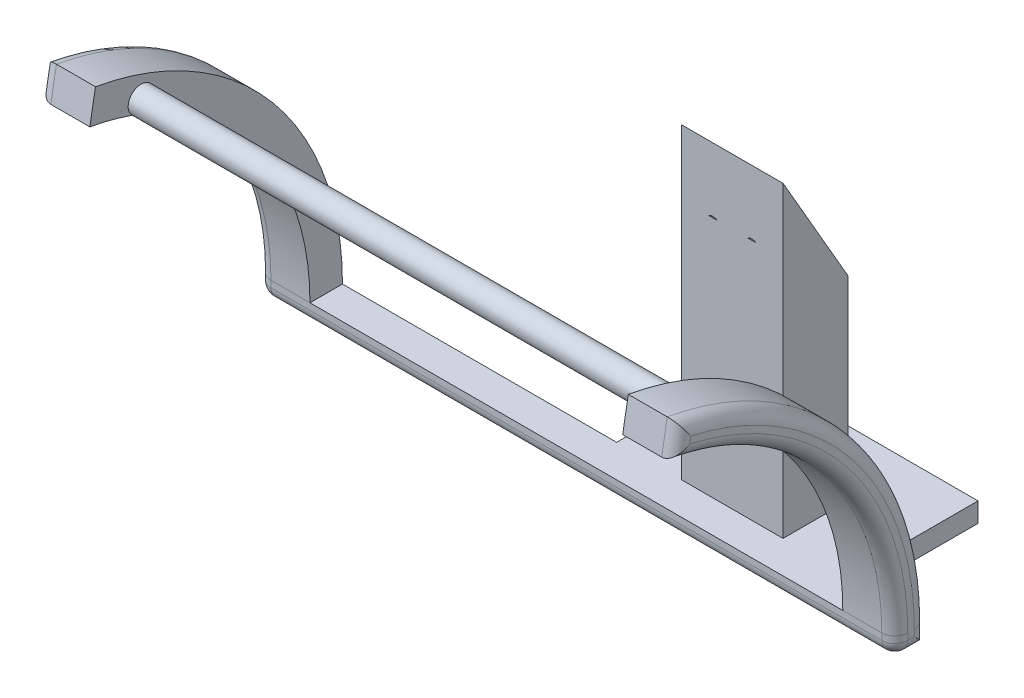
SolidWorks part; units mm, degrees
ref_plane "Front Plane" through (0, 0, 0) normal (0, 0, 1) x (1, 0, 0)
ref_plane "Top Plane" through (0, 0, 0) normal (0, 1, 0) x (1, 0, 0)
ref_plane "Right Plane" through (0, 0, 0) normal (1, 0, 0) x (0, 0, -1)
sketch "Sketch1" plane through (0, 0, 0) normal (0, 1, 0) x (1, 0, 0)
  line L0 (-8.4368, 20.25) -> (-8.4368, 0.25) construction
  line L1 (-26.2418, 20.25) -> (9.3682, 20.25)
  line L2 (-26.2418, 20.25) -> (-26.2418, 0.25)
  line L3 (-26.2418, 0.25) -> (9.3682, 0.25)
  line L4 (9.3682, 20.25) -> (9.3682, 0.25)
  line L5 (-38.4368, 0.25) -> (21.5632, 0.25)
  line L6 (-38.4368, 0.25) -> (-38.4368, -4.75)
  line L7 (-38.4368, -4.75) -> (21.5632, -4.75)
  line L8 (21.5632, 0.25) -> (21.5632, -4.75)
  line L9 (-23.1313, 20.25) -> (6.2616, 20.25) construction
  line L11 (-38.4368, -4.75) -> (-76.4368, -4.75)
  line L12 (-38.4368, -4.75) -> (-38.4368, 0.25)
  line L13 (-38.4368, 0.25) -> (-76.4368, 0.25)
  line L14 (-76.4368, -4.75) -> (-76.4368, 0.25)
  point P10 (-8.4368, 0.25)
  dimension "D1" = 20
  dimension "D2" = 35.61
  dimension "D3" = 60
  dimension "D4" = 5
  dimension "D5" = 38
extrude "Boss-Extrude1" add sketch "Sketch1" along normal blind 3 contours L8 L5 L3 L6 L7 | L1 L0 L5 L4 | L0 L1 L2 L3 | L12 L11 L14 L13 region at (0.4657, 0, -10.25) region at (-17.3393, 0, -10.25) region at (-8.4368, 0, 2.25)
ref_plane "Plane1" through (21.5632, 0, 0) normal (1, 0, 0) x (0, 0, -1)
sketch "Sketch2" plane through (21.5632, 0, 0) normal (1, 0, 0) x (0, 0, -1)
  line L0 (-4.75, 3) -> (-30.75, 3) construction
  line L1 (-30.75, 3) -> (-45.75, 3) construction
  line L2 (-37.7622, 48.3012) -> (-38.6304, 43.3771)
  line L3 (-4.75, 3) -> (0.25, 3)
  circle A0 centre (-45.75, 3) radius 22.5 construction
  arc A1 (-4.75, 3) -> (-38.6304, 43.3771) centre (-45.75, 3) ccw
  arc A2 (0.25, 3) -> (-37.7622, 48.3012) centre (-45.75, 3) ccw
  point P9 (0, 0)
  point P10 (-49.75, 3)
  dimension "D3" = 45
  dimension "D1" = 26
  dimension "D2" = 15
ref_plane "Plane2" through (-8.4368, 0, 0) normal (1, 0, 0) x (0, 0, -1)
sketch "Sketch3" plane through (0, 0, 0) normal (0, -1, 0) x (1, 0, 0)
  circle A0 centre (-20.4847, -8.75) radius 1.5
  circle A1 centre (-8.4349, -16.25) radius 1.5
  circle A2 centre (3.6149, -8.75) radius 1.5
  dimension "D1" = 3
extrude "Cut-Extrude1" cut sketch "Sketch3" against normal blind 5
sketch "Sketch7" plane through (0, 3, 0) normal (0, 1, 0) x (1, 0, 0)
  line L0 (-26.2418, 20.25) -> (-26.2418, 0.25) construction
  line L1 (-16.2418, 10.25) -> (-0.6318, 10.25)
  line L2 (-16.2418, 10.25) -> (-16.2418, 0.25)
  line L3 (-16.2418, 0.25) -> (-0.6318, 0.25)
  line L4 (-0.6318, 10.25) -> (-0.6318, 0.25)
  line L5 (9.3682, 20.25) -> (9.3682, 0.25) construction
  line L6 (-38.4368, -4.75) -> (21.5632, -4.75) construction
  dimension "D1" = 10
  dimension "D2" = 10
  dimension "D3" = 5
  dimension "D4" = 10
extrude "Boss-Extrude4" add sketch "Sketch7" along normal blind 30
sketch "Sketch8" plane through (-16.2418, 0, 0) normal (-1, 0, 0) x (0, 0, 1)
  line L0 (-10.25, 33) -> (-0.25, 50.3205)
  line L1 (-0.25, 33) -> (-0.25, 50.3205)
  line L2 (-10.25, 33) -> (-0.25, 33) construction
  line L3 (-10.25, 33) -> (-0.25, 33)
  dimension "D1" = 60
extrude "Boss-Extrude5" add sketch "Sketch8" against normal up to surface (15.61 mm away) up to face at (-0.6318, 18, -5.25)
sketch "Sketch9" plane through (0, 12.6884, -21.9769) normal (0, 0.5, -0.866) x (1, 0, 0)
  line L0 (-16.2418, -33.4538) -> (-0.6318, -33.4538) construction
  line L1 (-16.2418, -43.4538) -> (-16.2418, -23.4538) construction
  line L2 (-0.6318, -23.4538) -> (-0.6318, -43.4538) construction
  line L3 (-8.4368, -23.4538) -> (-8.4368, -43.4538) construction
  line L4 (-0.6318, -23.4538) -> (-16.2418, -23.4538) construction
  line L5 (-0.6318, -43.4538) -> (-16.2418, -43.4538) construction
  circle A0 centre (-11.4368, -33.4538) radius 1.5
  circle A1 centre (-5.4368, -33.4538) radius 1.5
  dimension "D1" = 3
  dimension "D2" = 3
  dimension "D3" = 6
  dimension "D4" = 3
extrude "Cut-Extrude2" cut sketch "Sketch9" against normal blind 5
extrude "Boss-Extrude6" add sketch "Sketch2" against normal blind 8
ref_plane "Plane3" through (-27.4368, 0, 0) normal (-1, 0, 0) x (0, 0, 1)
mirror "Mirror1" about plane through (-27.4368, 0, 0) normal (-1, 0, 0) of "Boss-Extrude6"
fillet "Fillet4" radius 2 13 edges at (-76.4368, 1.5, -0.25) (-76.4368, 32.5682, 10.512) (-76.4368, 45.8391, 38.1963) (-76.4368, 29.3543, 14.3422) (-76.4368, 1.5, 4.75) (-76.4368, 0, 2.25) (21.5632, 1.5, 4.75) (21.5632, 29.3543, 14.3422) (21.5632, 45.8391, 38.1963) (21.5632, 32.5682, 10.512) (21.5632, 1.5, -0.25) (21.5632, 0, 2.25) (-27.4368, 0, 4.75)
sketch "Sketch10" plane through (-68.4368, 0, 0) normal (1, 0, 0) x (0, 0, -1)
  line L0 (-22.8312, 42.884) -> (-23.762, 37.6053)
  line L1 (-38.6304, 43.3771) -> (-22.8312, 42.884) construction
  line L2 (-4.75, 3) -> (0.25, 3)
  line L3 (-37.7622, 48.3012) -> (-38.6304, 43.3771)
  line L4 (-4.75, 3) -> (0.25, 3)
  line L5 (-37.7622, 48.3012) -> (-38.6304, 43.3771)
  line L6 (-23.762, 37.6053) -> (-37.7622, 48.3012) construction
  circle A0 centre (-30.7308, 43.1305) radius 2
  arc A2 (-4.75, 3) -> (-38.6304, 43.3771) centre (-45.75, 3) ccw
  arc A3 (0.25, 3) -> (-37.7622, 48.3012) centre (-45.75, 3) ccw
  arc A4 (-4.75, 3) -> (-38.6304, 43.3771) centre (-45.75, 3) ccw
  arc A5 (0.25, 3) -> (-37.7622, 48.3012) centre (-45.75, 3) ccw
  dimension "D2" = 4
  dimension "D1" = 0
extrude "Boss-Extrude7" add sketch "Sketch10" along normal up to surface (82 mm away) contours A0 region at (-68.4368, 43.1523, 30.7227) up to face at (13.5632, 27.6904, 16.3251)
